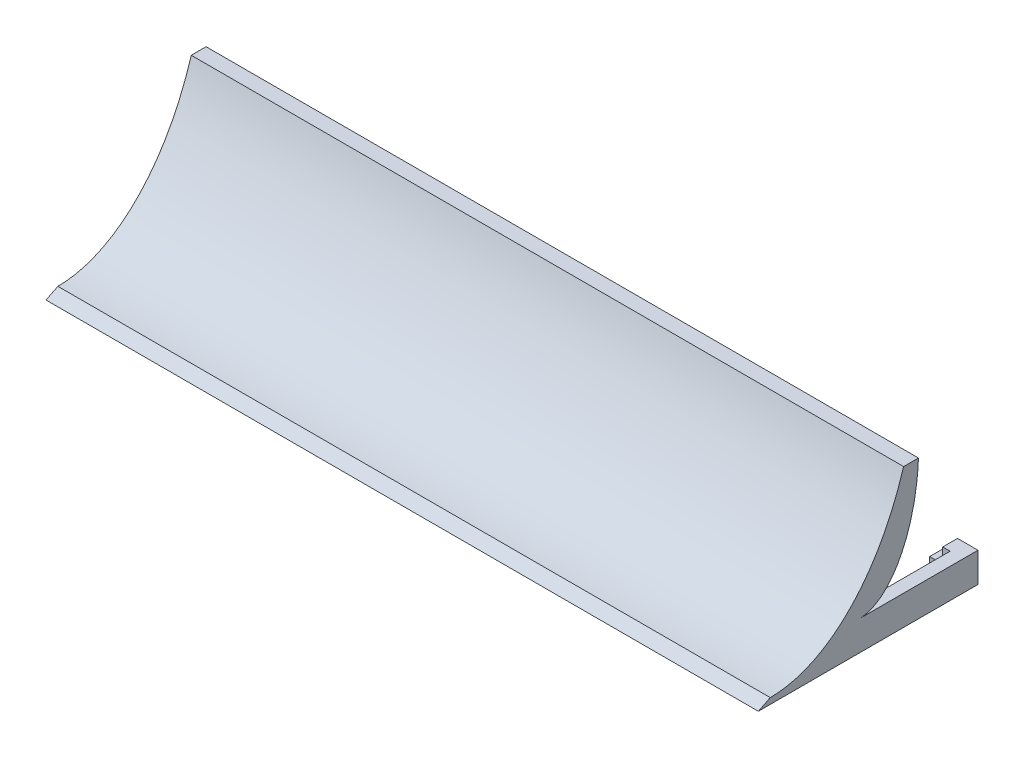
SolidWorks part; units mm, degrees
ref_plane "Alzado" through (0, 0, 0) normal (0, 0, 1) x (1, 0, 0)
ref_plane "Planta" through (0, 0, 0) normal (0, 1, 0) x (1, 0, 0)
ref_plane "Vista lateral" through (0, 0, 0) normal (1, 0, 0) x (0, 0, -1)
sketch "Croquis4" plane through (0, 0, 0) normal (1, 0, 0) x (0, 0, -1)
  line L0 (33.8376, 0) -> (-70.9068, 0) construction
  line L1 (0, -18.282) -> (0, 71.3339) construction
  line L2 (9.9706, 23.4676) -> (7.4706, 23.4676)
  line L4 (0, 0) -> (0, 5)
  line L7 (-15, 1) -> (-15, 81) construction
  line L8 (0, 0) -> (-17, 0)
  line L9 (-15, 1) -> (-17, 0)
  ellipse E0 centre (0, 25) end of major axis (0, 5) minor radius 10 (0, 5) -> (9.9706, 23.4676) ccw
  ellipse E1 centre (-15, 41) end of major axis (-15, 1) minor radius 25 (-15, 1) -> (7.4706, 23.4676) ccw
  dimension "D1" = 2
  dimension "D3" = 10
  dimension "D4" = 20
  dimension "D5" = 40
  dimension "D6" = 25
  dimension "D7" = 1
  dimension "D8" = 15
  dimension "D9" = 2.5
extrude "Cuchilla-Saliente" add sketch "Croquis4" along normal blind 60 and the other way blind 60
sketch "Encaje-Cuchilla-Lateral-Croquis-1" plane through (60, 0, 0) normal (1, 0, 0) x (0, 0, -1)
  line L1 (0, 0) -> (20, 0)
  line L2 (0, 0) -> (0, 5)
  line L3 (0, 5) -> (20, 5)
  line L4 (20, 0) -> (20, 5)
  dimension "D1" = 20
extrude "Encaje-Cuchilla-Lateral-Saliente-1" add sketch "Encaje-Cuchilla-Lateral-Croquis-1" against normal blind 2.2
sketch "Encaje-Cuchilla-Lateral-Croquis-2" plane through (57.8, 0, 0) normal (-1, 0, 0) x (0, 0, 1)
  line L0 (-20, 0) -> (-20, 5) construction
  line L1 (0, 0) -> (-20, 0)
  line L2 (0, 0) -> (0, 2.5)
  line L3 (0, 2.5) -> (-20, 2.5)
  line L4 (-20, 0) -> (-20, 2.5)
extrude "Encaje-Cuchilla-Lateral-Saliente-2" add sketch "Encaje-Cuchilla-Lateral-Croquis-2" along normal blind 2.2
sketch "Encaje-Cuchilla-Lateral-Croquis-3" plane through (55.6, 0, 0) normal (-1, 0, 0) x (0, 0, 1)
  line L1 (-20, 2.5) -> (-17.5, 2.5)
  line L2 (-20, 2.5) -> (-20, 1.25)
  line L3 (-20, 1.25) -> (-17.5, 1.25)
  line L4 (-17.5, 2.5) -> (-17.5, 1.25)
  dimension "D1" = 2.5
extrude "Encaje-Cuchilla-Lateral-Saliente-3" add sketch "Encaje-Cuchilla-Lateral-Croquis-3" along normal blind 1.25
sketch "Encaje-Cuchilla-Lateral-Croquis-4" plane through (57.8, 0, 0) normal (-1, 0, 0) x (0, 0, 1)
  line L1 (-20, 5) -> (-17.5, 5)
  line L2 (-20, 5) -> (-20, 3.75)
  line L3 (-20, 3.75) -> (-17.5, 3.75)
  line L4 (-17.5, 5) -> (-17.5, 3.75)
  dimension "D1" = 2.5
  dimension "D2" = 1.25
extrude "Encaje-Cuchilla-Lateral-Saliente-4" add sketch "Encaje-Cuchilla-Lateral-Croquis-4" along normal blind 1.25 contours L2 L1 L4 L3
sketch "Encaje-Cuchilla-Lateral-Croquis-5" plane through (-60, 0, 0) normal (-1, 0, 0) x (0, 0, 1)
  line L1 (0, 0) -> (-20, 0)
  line L2 (0, 0) -> (0, 5)
  line L3 (0, 5) -> (-20, 5)
  line L4 (-20, 0) -> (-20, 5)
extrude "Encaje-Cuchilla-Lateral-Saliente-5" add sketch "Encaje-Cuchilla-Lateral-Croquis-5" against normal blind 2.2 separate body
sketch "Encaje-Cuchilla-Lateral-Croquis-6" plane through (-57.8, 0, 0) normal (1, 0, 0) x (0, 0, -1)
  line L1 (20, 0) -> (0, 0)
  line L2 (20, 0) -> (20, 2.5)
  line L3 (20, 2.5) -> (0, 2.5)
  line L4 (0, 0) -> (0, 2.5)
extrude "Encaje-Cuchilla-Lateral-Saliente-6" add sketch "Encaje-Cuchilla-Lateral-Croquis-6" along normal blind 2.2
sketch "Encaje-Cuchilla-Lateral-Croquis-7" plane through (-57.8, 0, 0) normal (1, 0, 0) x (0, 0, -1)
  line L1 (20, 5) -> (17.5, 5)
  line L2 (20, 5) -> (20, 3.75)
  line L3 (20, 3.75) -> (17.5, 3.75)
  line L4 (17.5, 5) -> (17.5, 3.75)
  dimension "D1" = 2.5
  dimension "D2" = 1.25
extrude "Encaje-Cuchilla-Lateral-Saliente-7" add sketch "Encaje-Cuchilla-Lateral-Croquis-7" along normal blind 1.25
sketch "Encaje-Cuchilla-Lateral-Croquis-8" plane through (-55.6, 0, 0) normal (1, 0, 0) x (0, 0, -1)
  line L0 (20, 0) -> (20, 5) construction
  line L1 (20, 2.5) -> (17.5, 2.5)
  line L2 (20, 2.5) -> (20, 1.25)
  line L3 (20, 1.25) -> (17.5, 1.25)
  line L4 (17.5, 2.5) -> (17.5, 1.25)
  dimension "D1" = 2.5
  dimension "D2" = 1.25
extrude "Encaje-Cuchilla-Lateral-Saliente-8" add sketch "Encaje-Cuchilla-Lateral-Croquis-8" along normal blind 1.25
sketch "Encaje-Cuchilla-Central-Croquis" plane through (0, 0, 0) normal (0, 0, -1) x (-1, 0, 0)
  line L0 (0, 0) -> (0, 5) construction
  line L1 (55.6, 0) -> (-55.6, 0) construction
  line L2 (57.8, 5) -> (-57.8, 5) construction
  line L3 (2.5, 3.125) -> (5, 3.125)
  line L4 (2.5, 0) -> (-2.5, 0)
  line L5 (2.5, 0) -> (2.5, 1.875)
  line L6 (2.5, 5) -> (-2.5, 5)
  line L7 (-2.5, 0) -> (-2.5, 1.875)
  line L8 (2.5, 0) -> (-2.5, 5) construction
  line L9 (2.5, 5) -> (-2.5, 0) construction
  line L10 (-5, 1.875) -> (-2.5, 1.875)
  line L11 (-5, 1.875) -> (-5, 3.125)
  line L12 (-5, 3.125) -> (-2.5, 3.125)
  line L13 (5, 1.875) -> (5, 3.125)
  line L14 (-5, 1.875) -> (5, 3.125) construction
  line L15 (-5, 3.125) -> (5, 1.875) construction
  line L16 (-2.5, 3.125) -> (-2.5, 5)
  line L17 (2.5, 3.125) -> (2.5, 5)
  line L18 (2.5, 1.875) -> (5, 1.875)
  point P6 (0, 2.5)
  point P11 (0, 2.5)
  dimension "D1" = 5
  dimension "D2" = 10
  dimension "D3" = 1.25
extrude "Encaje-Cuchilla-Central-Saliente" add sketch "Encaje-Cuchilla-Central-Croquis" along normal blind 20
